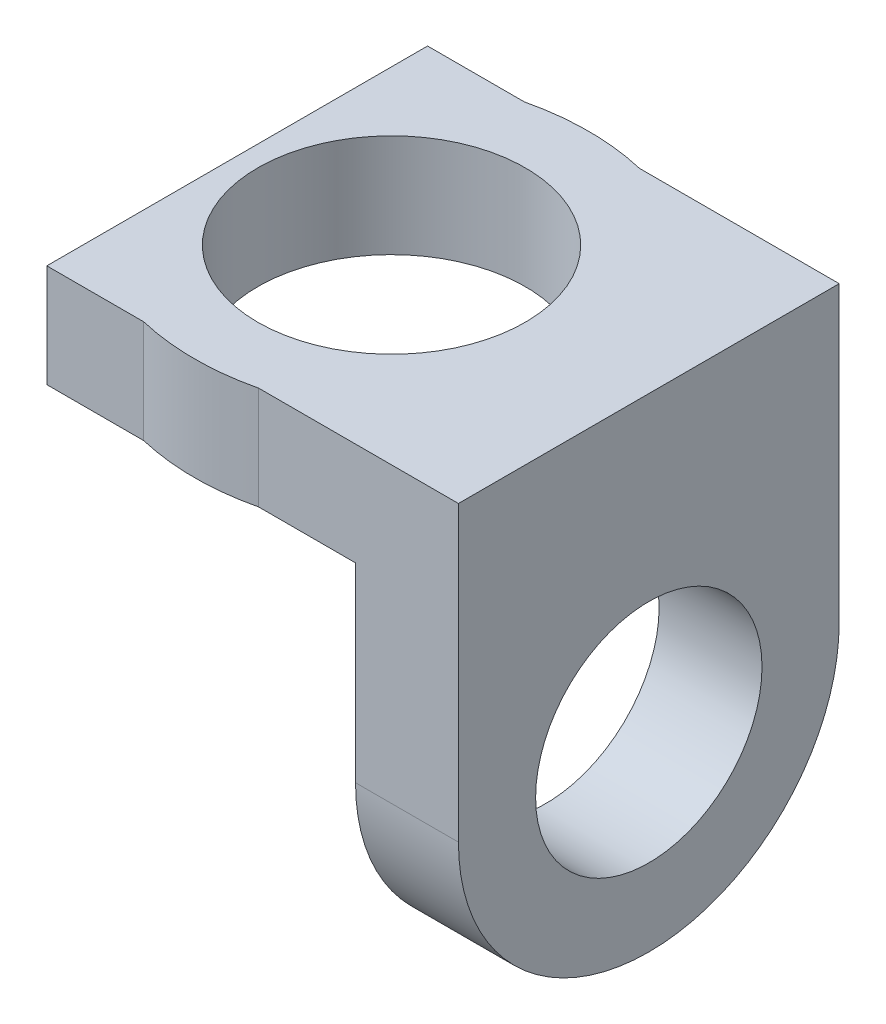
SolidWorks part; units mm, degrees
note: The reader was unsure of these and kept them because the rebuilt part matched: shared geometry of "Sketch2<3>".
ref_plane "Front Plane" through (0, 0, 0) normal (0, 0, 1) x (1, 0, 0)
ref_plane "Top Plane" through (0, 0, 0) normal (0, 1, 0) x (1, 0, 0)
ref_plane "Right Plane" through (0, 0, 0) normal (1, 0, 0) x (0, 0, -1)
sketch "Sketch1" plane through (0, 0, 0) normal (1, 0, 0) x (0, 0, -1)
  circle A0 centre (0, 0) radius 11
  circle A1 centre (0, 0) radius 18.5
  dimension "D1" = 22
  dimension "D2" = 7.5
extrude "Boss-Extrude1" add sketch "Sketch1" along normal blind 10
ref_plane "Plane1" through (0, 18.5, 0) normal (0, 1, 0) x (1, 0, 0)
sketch "Sketch2" plane through (0, 18.5, 0) normal (0, 1, 0) x (1, 0, 0)
  line L0 (10, -18.5) -> (10, 18.5) construction
  line L1 (10, -18.5) -> (10, 18.5)
  line L2 (0, 18.5) -> (0, -18.5) construction
  line L3 (0, 18.5) -> (0, -18.5)
  line L4 (10, -18.5) -> (-30, -18.5)
  line L5 (-30, -18.5) -> (-30, 18.5)
  line L6 (-30, 18.5) -> (10, 18.5)
  line L7 (-15, 0) -> (-42.2528, 0) construction
  circle A0 centre (-15, 0) radius 11
  circle A1 centre (-15, 0) radius 13
  arc A2 (-9.412, -18.5) -> (-20.588, -18.5) centre (-15, 5.0473) cw
  arc A3 (-9.412, 18.5) -> (-20.588, 18.5) centre (-15, -5.0473) ccw
  point P12 (-15, -19.154)
  dimension "D2" = 22
  dimension "D3" = 2
  dimension "D4" = 2
  dimension "D1" = 40
extrude "Boss-Extrude2" add sketch "Sketch2" against normal up to surface (18.5 mm away) contours L6 L3 L4 L1
extrude "Boss-Extrude3" add sketch "Sketch2<3>" along normal blind 10 contours L6 L5 L4 L3 | L6 L3 L4 L1 | A1 L5 L4 | A1 L6 L5 | L6 A3 | A2 L4
sketch "Sketch2<3>" plane through (0, 18.5, 0) normal (0, 1, 0) x (1, 0, 0) same geometry as "Sketch2"
ref_point "Point1"
